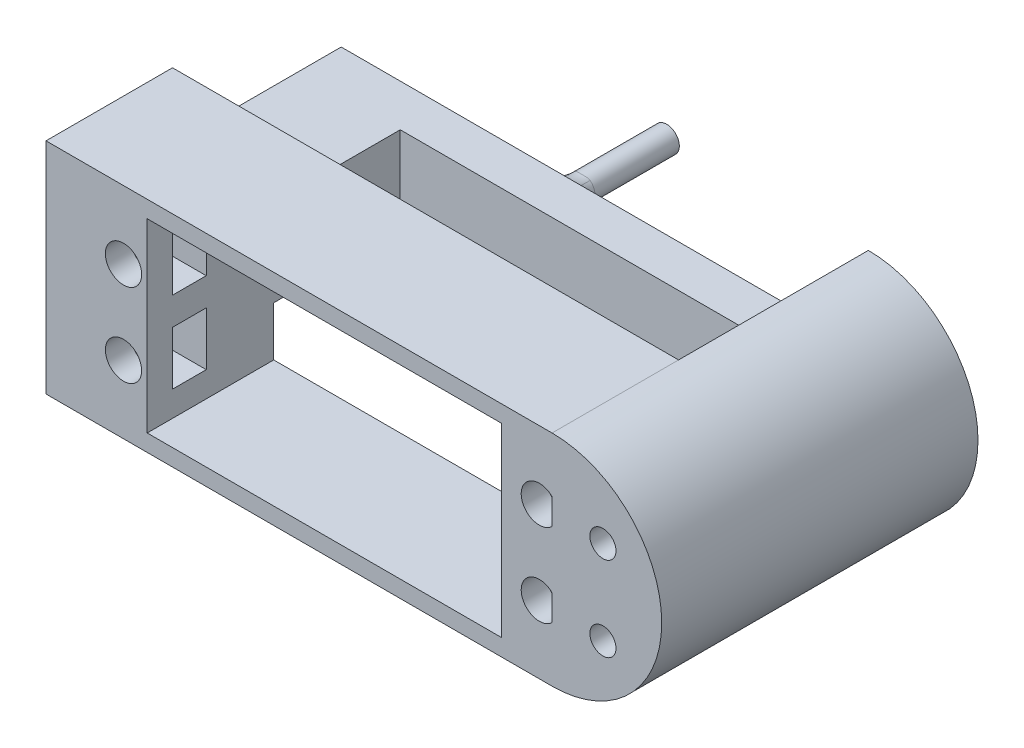
SolidWorks part; units mm, degrees
ref_plane "Plan de face" through (0, 0, 0) normal (0, 0, 1) x (1, 0, 0)
ref_plane "Plan de dessus" through (0, 0, 0) normal (0, 1, 0) x (1, 0, 0)
ref_plane "Plan de droite" through (0, 0, 0) normal (1, 0, 0) x (0, 0, -1)
sketch "Esquisse1" plane through (0, 0, 0) normal (0, 0, 1) x (1, 0, 0)
  line L1 (30, -13) -> (-30, -13)
  line L3 (30, 13) -> (-30, 13)
  line L4 (-30, -13) -> (-30, 13)
  line L5 (30, -13) -> (-30, 13) construction
  line L6 (30, 13) -> (-30, -13) construction
  arc A0 (30, -13) -> (30, 13) centre (30, 0) ccw
  point P0 (0, 0)
  dimension "D1" = 60
  dimension "D2" = 26
extrude "Boss.-Extru.1" add sketch "Esquisse1" along normal blind 15
sketch "Esquisse2" plane through (0, 0, 15) normal (0, 0, 1) x (1, 0, 0)
  line L0 (-30, 13) -> (-30, -13) construction
  line L1 (-18, 11) -> (24, 11)
  line L2 (-18, 11) -> (-18, -11)
  line L3 (-18, -11) -> (24, -11)
  line L4 (24, 11) -> (24, -11)
  point P4 (-18, 0)
  dimension "D1" = 42
  dimension "D2" = 22
  dimension "D3" = 12
extrude "Enlèv. mat.-Extru.1" cut sketch "Esquisse2" against normal through all
sketch "Esquisse4" plane through (0, 0, 15) normal (0, 0, 1) x (1, 0, 0)
  circle A0 centre (-20.81, 4.935) radius 2.15
  circle A1 centre (-20.81, -4.935) radius 2.15
  circle A2 centre (28.49, 4.935) radius 2.15
  circle A3 centre (28.49, -4.935) radius 2.15
extrude "Enlèv. mat.-Extru.2" cut sketch "Esquisse4" against normal blind 3
sketch "Esquisse5" plane through (-18, 0, 0) normal (1, 0, 0) x (0, 0, -1)
  line L1 (-12, -8) -> (-8, -8)
  line L2 (-12, -8) -> (-12, -1.65)
  line L3 (-12, -1.65) -> (-8, -1.65)
  line L4 (-8, -8) -> (-8, -1.65)
  line L5 (-15, 11) -> (-15, -11) construction
  line L6 (0, -11) -> (-15, -11) construction
  line L7 (-16.3207, 0) -> (1.751, 0) construction
  line L8 (-12, 1.65) -> (-8, 1.65)
  line L9 (-8, 8) -> (-8, 1.65)
  line L10 (-12, 8) -> (-8, 8)
  line L11 (-12, 8) -> (-12, 1.65)
  dimension "D1" = 6.35
  dimension "D2" = 4
  dimension "D3" = 3
  dimension "D4" = 3
extrude "Enlèv. mat.-Extru.3" cut sketch "Esquisse5" against normal blind 6
sketch "Esquisse6" plane through (24, 0, 0) normal (-1, 0, 0) x (0, 0, 1)
  line L0 (15, -11) -> (15, 11) construction
  line L1 (12, 8) -> (8, 8)
  line L2 (12, 8) -> (12, 1.65)
  line L3 (12, 1.65) -> (8, 1.65)
  line L4 (8, 8) -> (8, 1.65)
  line L5 (0, 11) -> (15, 11) construction
  line L6 (16.3207, 0) -> (-2.2889, 0) construction
  line L7 (12, -1.65) -> (8, -1.65)
  line L8 (8, -8) -> (8, -1.65)
  line L9 (12, -8) -> (8, -8)
  line L10 (12, -8) -> (12, -1.65)
  dimension "D1" = 6.35
  dimension "D2" = 4
  dimension "D3" = 3
  dimension "D4" = 3
extrude "Enlèv. mat.-Extru.4" cut sketch "Esquisse6" against normal blind 8
sketch "Esquisse10" plane through (0, 0, 0) normal (0, 0, -1) x (-1, 0, 0)
  line L0 (30, 13) -> (30, -13) construction
  line L1 (18, 0) -> (30, 0) construction
  line L2 (18, 11) -> (18, -11) construction
  line L3 (-24, 0) -> (-43, 0) construction
  line L4 (30, -5.1328) -> (18, -5.1328)
  line L5 (30, -5.1328) -> (30, 5.1328)
  line L6 (30, 5.1328) -> (18, 5.1328)
  line L7 (18, -5.1328) -> (18, 5.1328)
  line L8 (30, -5.1328) -> (18, 5.1328) construction
  line L9 (30, 5.1328) -> (18, -5.1328) construction
  line L10 (-24, -11) -> (-24, 11) construction
  line L11 (-24, 5.1328) -> (-41.9438, 5.1328)
  line L12 (-24, -5.1328) -> (-41.9438, -5.1328)
  line L13 (-24, 5.1328) -> (-24, -5.1328)
  arc A0 (-30, 13) -> (-30, -13) centre (-30, 0) ccw construction
  arc A1 (-41.9438, 5.1328) -> (-41.9438, -5.1328) centre (-30, 0) ccw
  point P9 (24, 0)
extrude "Boss.-Extru.6" add sketch "Esquisse10" along normal blind 20
sketch "Esquisse11" plane through (0, 0, -20) normal (0, 0, -1) x (-1, 0, 0)
  line L1 (-24, 5.1328) -> (18, 5.1328)
  line L2 (-24, 5.1328) -> (-24, -5.1328)
  line L3 (-24, -5.1328) -> (18, -5.1328)
  line L4 (18, 5.1328) -> (18, -5.1328)
extrude "Boss.-Extru.7" add sketch "Esquisse11" against normal blind 5
sketch "Esquisse12" plane through (0, 0, -20) normal (0, 0, -1) x (-1, 0, 0)
  line L0 (-30, -13) -> (-30, 13)
  arc A0 (-30, 13) -> (-41.9438, 5.1328) centre (-30, 0) ccw construction
  arc A1 (-41.9438, 5.1328) -> (-41.9438, -5.1328) centre (-30, 0) ccw construction
  arc A2 (-41.9438, -5.1328) -> (-30, -13) centre (-30, 0) ccw construction
  arc A3 (-30, 13) -> (-41.9438, 5.1328) centre (-30, 0) ccw
  arc A4 (-41.9438, 5.1328) -> (-41.9438, -5.1328) centre (-30, 0) ccw
  arc A5 (-41.9438, -5.1328) -> (-30, -13) centre (-30, 0) ccw
extrude "Boss.-Extru.8" add sketch "Esquisse12" against normal blind 35 and the other way blind 2.5
sketch "Esquisse13" plane through (0, 0, 15) normal (0, 0, 1) x (1, 0, 0)
  circle A0 centre (36.0309, 4.6665) radius 1.55
  circle A1 centre (36.0309, -5.3335) radius 1.55
  dimension "D1" = 3.1
  dimension "D2" = 3.1
  dimension "D3" = 10
extrude "Enlèv. mat.-Extru.5" cut sketch "Esquisse13" against normal through all and the other way through all
sketch "Esquisse14" plane through (0, 0, 15) normal (0, 0, 1) x (1, 0, 0)
  line L0 (33.1601, 12.6101) -> (33.1601, -12.6101)
  arc A0 (30, -13) -> (30, 13) centre (30, 0) ccw construction
  arc A1 (33.1601, -12.6101) -> (33.1601, 12.6101) centre (30, 0) ccw
extrude "Boss.-Extru.9" [suppressed] add sketch "Esquisse14" along normal blind 2.5
fillet "Congé1" [suppressed] radius 1
sketch "Esquisse15" plane through (0, 0, -20) normal (0, 0, -1) x (-1, 0, 0)
  circle A0 centre (6.41, 0) radius 1.5
  dimension "D1" = 3
extrude "Boss.-Extru.10" add sketch "Esquisse15" along normal blind 15
fillet "Congé2" radius 5 1 edges at (-7.91, 0, -20)
